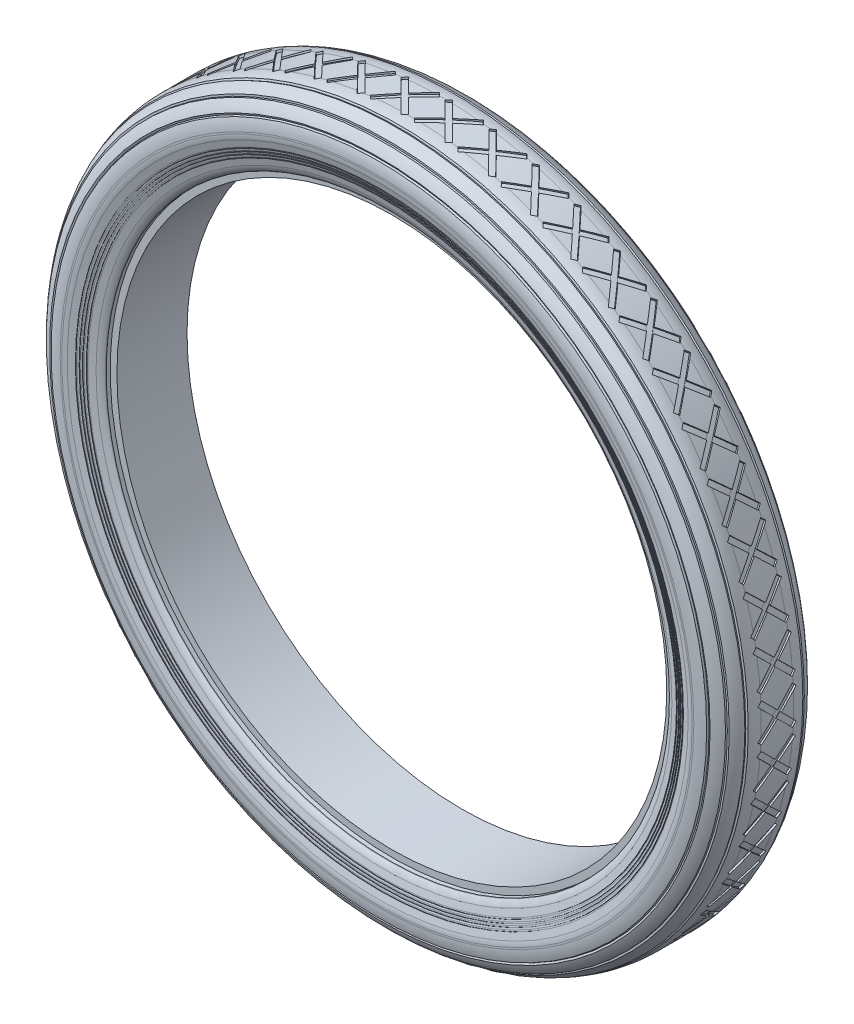
SolidWorks part; units mm, degrees
ref_plane "Спереди" through (0, 0, 0) normal (0, 0, 1) x (1, 0, 0)
ref_plane "Сверху" through (0, 0, 0) normal (0, 1, 0) x (1, 0, 0)
ref_plane "Справа" through (0, 0, 0) normal (1, 0, 0) x (0, 0, -1)
sketch "Эскиз2" plane through (0, 0, 0) normal (1, 0, 0) x (0, 0, -1)
  line L0 (-10.4188, 260) -> (10.4188, 260)
  line L1 (-26, 203.9173) -> (-26, 208.9173)
  line L2 (26, 203.9173) -> (26, 208.9173)
  line L3 (0, 193.4825) -> (0, 265.3732) construction
  line L4 (-26, 203.9173) -> (26, 203.9173)
  line L5 (-37, 233.7884) -> (-37, 235)
  line L6 (-12, 260) -> (-10.4188, 260)
  line L7 (10.4188, 260) -> (12, 260)
  line L8 (-70.3305, 0) -> (169.6506, 0) construction
  line L9 (37, 235) -> (37, 233.7884)
  line L10 (-26, 208.9173) -> (-29, 208.9173)
  line L11 (26, 208.9173) -> (29, 208.9173)
  line L12 (-29, 208.9173) -> (-29.2706, 209.1879)
  line L13 (29, 208.9173) -> (29.2706, 209.1879)
  line L14 (-36.5171, 230.278) -> (-35.193, 225.557)
  line L15 (36.5171, 230.278) -> (35.193, 225.557)
  line L16 (29.0445, 251.9036) -> (30.4192, 251.9036)
  line L17 (-29.0445, 251.9036) -> (-30.4192, 251.9036)
  line L18 (-29.0445, 251.9036) -> (-29.0445, 253.2889)
  line L19 (29.0445, 251.9036) -> (29.0445, 253.2889)
  line L20 (20.7927, 257.3313) -> (20.2394, 258.6032)
  line L21 (-20.7927, 257.3313) -> (-22.0646, 257.8846)
  line L22 (-20.7927, 257.3313) -> (-20.2394, 258.6032)
  line L23 (20.7927, 257.3313) -> (22.0646, 257.8846)
  line L24 (34.3649, 243.7069) -> (35.6347, 243.1488)
  line L25 (-34.3649, 243.7069) -> (-34.923, 244.9767)
  line L26 (-34.3649, 243.7069) -> (-35.6347, 243.1488)
  line L27 (34.3649, 243.7069) -> (34.923, 244.9767)
  line L28 (-34.923, 221.7078) -> (-32.3332, 222.4342) construction
  line L29 (-34.3076, 222.3997) -> (-33.8267, 222.5346)
  line L30 (-33.8267, 222.5346) -> (-34.0967, 223.4974)
  line L31 (-34.0967, 223.4974) -> (-34.5776, 223.3626)
  line L32 (-34.923, 224.5942) -> (-34.4416, 224.7292)
  line L33 (-34.4416, 224.7292) -> (-34.7116, 225.692)
  line L34 (-34.7116, 225.692) -> (-35.193, 225.557)
  line L35 (-32.6707, 218.4146) -> (-33.1521, 218.2796)
  line L36 (-32.9407, 219.3775) -> (-32.6707, 218.4146)
  line L37 (-33.4221, 219.2425) -> (-32.9407, 219.3775)
  line L38 (-34.0375, 221.4369) -> (-33.5567, 221.5717)
  line L39 (-33.5567, 221.5717) -> (-33.2866, 220.6089)
  line L40 (-33.2866, 220.6089) -> (-33.7675, 220.474)
  line L41 (-34.923, 224.5942) -> (-34.5776, 223.3626)
  line L42 (-34.3076, 222.3997) -> (-34.0375, 221.4369)
  line L43 (-33.7675, 220.474) -> (-33.4221, 219.2425)
  line L44 (-33.1521, 218.2796) -> (-31.8281, 213.5586)
  line L45 (32.6707, 218.4146) -> (33.1521, 218.2796)
  line L46 (32.9407, 219.3775) -> (32.6707, 218.4146)
  line L47 (33.4221, 219.2425) -> (32.9407, 219.3775)
  line L48 (33.2866, 220.6089) -> (33.7675, 220.474)
  line L49 (33.5567, 221.5717) -> (33.2866, 220.6089)
  line L50 (34.0375, 221.4369) -> (33.5567, 221.5717)
  line L51 (34.3076, 222.3997) -> (33.8267, 222.5346)
  line L52 (34.0967, 223.4974) -> (34.5776, 223.3626)
  line L53 (33.8267, 222.5346) -> (34.0967, 223.4974)
  line L54 (34.923, 224.5942) -> (34.4416, 224.7292)
  line L55 (34.4416, 224.7292) -> (34.7116, 225.692)
  line L56 (34.7116, 225.692) -> (35.193, 225.557)
  line L57 (34.923, 224.5942) -> (34.5776, 223.3626)
  line L58 (34.3076, 222.3997) -> (34.0375, 221.4369)
  line L59 (33.7675, 220.474) -> (33.4221, 219.2425)
  line L60 (33.1521, 218.2796) -> (31.8281, 213.5586)
  arc A0 (-37, 235) -> (-35.6347, 243.1488) centre (-12, 235) cw
  arc A1 (37, 235) -> (35.6347, 243.1488) centre (12, 235) ccw
  arc A2 (-36.5171, 230.278) -> (-37, 233.7884) centre (-24, 233.7884) cw
  arc A3 (37, 233.7884) -> (36.5171, 230.278) centre (24, 233.7884) cw
  arc A4 (29.2706, 209.1879) -> (31.8281, 213.5586) centre (22.1996, 216.259) ccw
  arc A5 (-31.8281, 213.5586) -> (-29.2706, 209.1879) centre (-22.1996, 216.259) ccw
  arc A6 (-29.0445, 253.2889) -> (-22.0646, 257.8846) centre (-12, 235) cw
  arc A7 (29.0445, 253.2889) -> (22.0646, 257.8846) centre (12, 235) ccw
  arc A8 (-20.2394, 258.6032) -> (-12, 260) centre (-12, 235) cw
  arc A9 (20.2394, 258.6032) -> (12, 260) centre (12, 235) ccw
  arc A10 (-34.923, 244.9767) -> (-30.4192, 251.9036) centre (-12, 235) cw
  arc A11 (34.923, 244.9767) -> (30.4192, 251.9036) centre (12, 235) ccw
  point P30 (31.1213, 211.0386)
  point P33 (-31.1213, 211.0386)
  dimension "D5" = 0.5
  dimension "D7" = 25
  dimension "D8" = 1
  dimension "D9" = 52
  dimension "D15" = 13
  dimension "D16" = 13
  dimension "D17" = 10
  dimension "D18" = 10
  dimension "D2" = 56.0827
  dimension "D3" = 1
  dimension "D6" = 5
  dimension "D10" = 26
  dimension "D11" = 3
  dimension "D12" = 3
  dimension "D13" = 3
  dimension "D14" = 3
  dimension "D19" = 0.5
revolve "Повернуть1" add sketch "Эскиз2" angle 360 about L8
ref_plane "Плоскость3" through (0, 0, 0) normal (0, -0.7071, 0.7071) x (1, 0, 0)
sketch "Эскиз5" plane through (0, 0, 0) normal (0, -0.7071, 0.7071) x (1, 0, 0)
  line L0 (0, 52.6375) -> (0, -43.4182) construction
  line L2 (-260, 2) -> (-260.4369, 2)
  line L3 (-260, 8.4853) -> (-260, -8.4853) construction
  line L4 (-260, 2) -> (-259, 2)
  line L5 (-259, 2) -> (-259, -2)
  line L6 (0, 49.7312) -> (0, -119.9611) construction
  line L7 (-260.4369, 2) -> (-260.4369, -2)
  line L8 (-260.4369, -2) -> (-260, -2)
  line L9 (-260, -2) -> (-259, -2)
  point P15 (-259, 0)
  dimension "D2" = 1
revolve "Вырез-Повернуть2" cut sketch "Эскиз5" angle 8 mid plane about L0
ref_plane "Плоскость4" through (0, 0, 0) normal (0, 0.7071, 0.7071) x (1, 0, 0)
sketch "Эскиз6" plane through (0, 0, 0) normal (0, 0.7071, 0.7071) x (1, 0, 0)
  line L0 (0, -32.7246) -> (0, 40.2475) construction
  line L1 (0, 0) -> (-276.6127, 0) construction
  line L3 (-259.8728, 2) -> (-258.8728, 2)
  line L4 (-258.8728, 2) -> (-258.8728, -2)
  line L5 (-259.8728, -2) -> (-258.8728, -2)
  line L6 (-259.8728, 2) -> (-260.5775, 2)
  line L7 (-260.5775, 2) -> (-260.5775, -2)
  line L8 (-260.5775, -2) -> (-259.8728, -2)
  point P10 (-259.8728, 0)
  point P11 (-258.8728, 0)
  dimension "D1" = 2
  dimension "D2" = 1
revolve "Вырез-Повернуть3" cut sketch "Эскиз6" angle 8 mid plane about L0
pattern_circular "Круговой массив6" count 50 every 7.2 about axis through (0, 0, 70.3305) along (0, 0, 1) of "Вырез-Повернуть2", "Вырез-Повернуть3"
